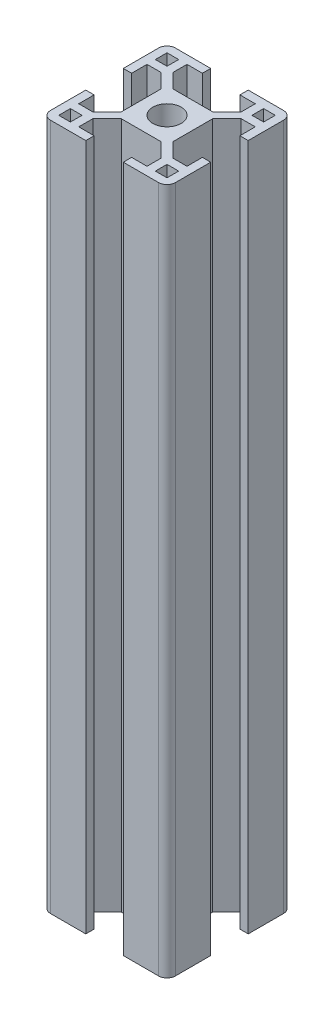
SolidWorks part; units mm, degrees
ref_plane "Front plane" through (0, 0, 0) normal (0, 0, 1) x (1, 0, 0)
ref_plane "Top plane" through (0, 0, 0) normal (0, 1, 0) x (1, 0, 0)
ref_plane "Right plane" through (0, 0, 0) normal (1, 0, 0) x (0, 0, -1)
ref_axis "Axis X" through (0, 0, 0) along (1, 0, 0)
ref_axis "Axis Y" through (0, 0, 0) along (0, 1, 0)
ref_axis "Axis Z" through (0, 0, 0) along (0, 0, 1)
sketch "Sketch1" plane through (0, 0, 0) normal (0, 1, 0) x (1, 0, 0)
  line L1 (-10, 10) -> (10, 10)
  line L2 (-10, 10) -> (-10, -10)
  line L3 (-10, -10) -> (10, -10)
  line L4 (10, 10) -> (10, -10)
  line L5 (-10, 10) -> (10, -10) construction
  line L6 (-10, -10) -> (10, 10) construction
  point P0 (0, 0)
  dimension "D1" = 20
  dimension "D2" = 20
extrude "Extrude1" add sketch "Sketch1" along normal blind 110
sketch "Sketch2" plane through (0, 110, 0) normal (0, 1, 0) x (1, 0, 0)
  line L0 (0, 0) -> (10, 0) construction
  line L1 (10, -10) -> (10, 10) construction
  line L2 (10, 10) -> (-10, 10) construction
  line L3 (8.6667, 3) -> (11.3333, 3)
  line L4 (8.6667, 3) -> (8.6667, -3) construction
  line L5 (8.6667, -3) -> (11.3333, -3)
  line L6 (11.3333, 3) -> (11.3333, -3)
  line L7 (8.6667, 3) -> (11.3333, -3) construction
  line L8 (8.6667, -3) -> (11.3333, 3) construction
  line L9 (6.8, 8.6667) -> (8.6667, 8.6667)
  line L10 (6.8, 8.6667) -> (6.8, 6.8)
  line L11 (6.8, 6.8) -> (8.6667, 6.8)
  line L12 (8.6667, 8.6667) -> (8.6667, 6.8)
  line L13 (6.8, 8.6667) -> (8.6667, 6.8) construction
  line L14 (6.8, 6.8) -> (8.6667, 8.6667) construction
  line L15 (0, 0) -> (10, 10) construction
  line L16 (8.6667, 3) -> (8.6667, 5.4667)
  line L17 (8.6667, 5.4667) -> (6.4095, 5.4667)
  line L18 (6.4095, 5.4667) -> (4.1333, 3.1905)
  line L19 (4.1333, 3.1905) -> (4.1333, -3.1905)
  line L20 (4.1333, -3.1905) -> (6.4095, -5.4667)
  line L21 (6.4095, -5.4667) -> (8.6667, -5.4667)
  line L22 (8.6667, -5.4667) -> (8.6667, -3)
  line L65 (-3.1905, 4.1333) -> (-5.4667, 6.4095)
  line L66 (-5.4667, 6.4095) -> (-5.4667, 8.6667)
  line L67 (-5.4667, 8.6667) -> (-3, 8.6667)
  line L68 (3, 11.3333) -> (-3, 11.3333)
  line L69 (-3, 8.6667) -> (-3, 11.3333)
  line L70 (3, 8.6667) -> (3, 11.3333)
  line L71 (3, 8.6667) -> (5.4667, 8.6667)
  line L72 (5.4667, 8.6667) -> (5.4667, 6.4095)
  line L73 (5.4667, 6.4095) -> (3.1905, 4.1333)
  line L74 (3.1905, 4.1333) -> (-3.1905, 4.1333)
  line L75 (0, 10) -> (0, -10) construction
  line L76 (-10, -10) -> (10, -10) construction
  line L77 (0, 0) -> (-10, 0) construction
  line L78 (-10, 10) -> (-10, -10) construction
  line L79 (8.6667, -8.6667) -> (8.6667, -6.8)
  line L80 (6.8, -6.8) -> (8.6667, -6.8)
  line L81 (6.8, -8.6667) -> (6.8, -6.8)
  line L82 (6.8, -8.6667) -> (8.6667, -8.6667)
  line L83 (-6.8, 6.8) -> (-8.6667, 6.8)
  line L84 (-8.6667, 8.6667) -> (-8.6667, 6.8)
  line L85 (-6.8, 8.6667) -> (-8.6667, 8.6667)
  line L86 (-6.8, 8.6667) -> (-6.8, 6.8)
  line L87 (-6.8, -8.6667) -> (-8.6667, -8.6667)
  line L88 (-6.8, -8.6667) -> (-6.8, -6.8)
  line L89 (-6.8, -6.8) -> (-8.6667, -6.8)
  line L90 (-8.6667, -8.6667) -> (-8.6667, -6.8)
  line L91 (-6.4095, -5.4667) -> (-8.6667, -5.4667)
  line L92 (-4.1333, -3.1905) -> (-6.4095, -5.4667)
  line L93 (-4.1333, 3.1905) -> (-4.1333, -3.1905)
  line L94 (-6.4095, 5.4667) -> (-4.1333, 3.1905)
  line L95 (-8.6667, 5.4667) -> (-6.4095, 5.4667)
  line L96 (-8.6667, 3) -> (-8.6667, 5.4667)
  line L97 (-8.6667, 3) -> (-11.3333, 3)
  line L98 (-11.3333, 3) -> (-11.3333, -3)
  line L99 (-8.6667, -3) -> (-11.3333, -3)
  line L100 (-8.6667, -5.4667) -> (-8.6667, -3)
  line L101 (3.1905, -4.1333) -> (-3.1905, -4.1333)
  line L102 (5.4667, -6.4095) -> (3.1905, -4.1333)
  line L103 (5.4667, -8.6667) -> (5.4667, -6.4095)
  line L104 (3, -8.6667) -> (5.4667, -8.6667)
  line L105 (3, -8.6667) -> (3, -11.3333)
  line L106 (3, -11.3333) -> (-3, -11.3333)
  line L107 (-3, -8.6667) -> (-3, -11.3333)
  line L108 (-5.4667, -8.6667) -> (-3, -8.6667)
  line L109 (-5.4667, -6.4095) -> (-5.4667, -8.6667)
  line L110 (-3.1905, -4.1333) -> (-5.4667, -6.4095)
  circle A0 centre (0, 0) radius 2.2667
  point P9 (7.7333, 7.7333)
  point P20 (7.5381, 5.4667)
  point P27 (10, -3)
  point P34 (-3, 10)
  point P37 (5.4667, 7.5381)
  dimension "D10" = 4.5333
  dimension "D1" = 2.6667
  dimension "D2" = 6
  dimension "D3" = 1.3333
  dimension "D4" = 1.3333
  dimension "D5" = 4.5333
  dimension "D6" = 5.4667
  dimension "D7" = 0.6667
  dimension "D8" = 1.3333
extrude "Extrude2" cut sketch "Sketch2" against normal through all
fillet "Fillet1" radius 1.3333 4 edges at (10, 55, 10) (10, 55, -10) (-10, 55, 10) (-10, 55, -10)
sketch "Эскиз3" plane through (0, 0, 0) normal (0, 0, 1) x (1, 0, 0)
  line L0 (0, 110) -> (0, 0) construction
  line L1 (3.1905, 110) -> (-3.1905, 110) construction
  line L2 (3.1905, 0) -> (-3.1905, 0) construction
  line L4 (-2.5, 57.5) -> (2.5, 57.5)
  line L5 (-2.5, 57.5) -> (-2.5, 52.5)
  line L6 (-2.5, 52.5) -> (2.5, 52.5)
  line L7 (2.5, 57.5) -> (2.5, 52.5)
  line L8 (-2.5, 57.5) -> (2.5, 52.5) construction
  line L9 (-2.5, 52.5) -> (2.5, 57.5) construction
  point P6 (0, 55)
  dimension "D1" = 5
  dimension "D2" = 5
extrude "Вырез-Вытянуть1" cut sketch "Эскиз3" against normal mid plane 20
equation "\"prof_width\"= 20'Aluminium profile parameters"
equation "\"D1@Sketch1\"=\"prof_width\""
equation "\"D2@Sketch1\"=\"prof_width\""
equation "\"prof_groove\"= 6"
equation "\"prof_length\"= 110"
equation "\"D1@Extrude1\"=\"prof_length\""
equation "\"D1@Sketch2\"=\"prof_width\"/30*4"
equation "\"D2@Sketch2\"=\"prof_groove\""
equation "\"D3@Sketch2\"=\"D1@Sketch2\"/2"
equation "\"D4@Sketch2\"=\"D3@Sketch2\""
equation "\"D5@Sketch2\"=\"prof_width\"/30*6.8"
equation "\"D6@Sketch2\"=\"prof_width\"/30*8.2"
equation "\"D7@Sketch2\"=\"D3@Sketch2\"/2"
equation "\"D8@Sketch2\"=\"D3@Sketch2\""
equation "\"D10@Sketch2\"=\"prof_width\"/30*6.8"
equation "\"D1@Fillet1\"=\"prof_width\"/30*2"
